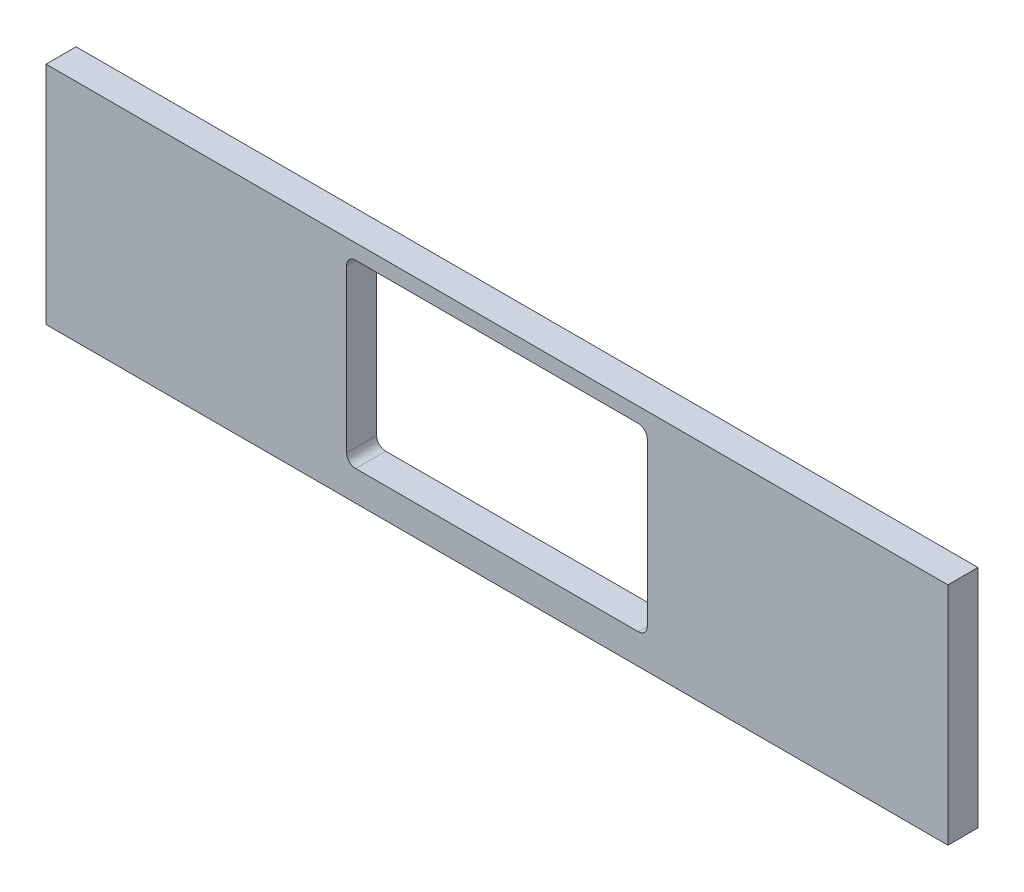
SolidWorks part; units mm, degrees
ref_plane "Ebene vorne" through (0, 0, 0) normal (0, 0, 1) x (1, 0, 0)
ref_plane "Ebene oben" through (0, 0, 0) normal (0, 1, 0) x (1, 0, 0)
ref_plane "Ebene rechts" through (0, 0, 0) normal (1, 0, 0) x (0, 0, -1)
sketch "Skizze1" plane through (0, 0, 0) normal (0, 0, 1) x (1, 0, 0)
  line L0 (-150, -75) -> (-150, 55) construction
  line L1 (150, -150) -> (-150, -150)
  line L2 (150, -150) -> (150, -75)
  line L3 (150, -75) -> (-150, -75)
  line L4 (-150, -150) -> (-150, -75)
  dimension "D1" = 75
extrude "Linear austragen1" add sketch "Skizze1" along normal blind 10
sketch "Skizze2" plane through (0, 0, 10) normal (0, 0, 1) x (1, 0, 0)
  line L0 (-150, -150) -> (150, -150) construction
  line L1 (50, -140) -> (-50, -140)
  line L2 (50, -140) -> (50, -80)
  line L3 (50, -80) -> (-50, -80)
  line L4 (-50, -140) -> (-50, -80)
  line L5 (50, -140) -> (150, -140) construction
  line L6 (150, 55) -> (150, -150) construction
  line L7 (-50, -140) -> (-150, -140) construction
  line L8 (-150, 55) -> (-150, -150) construction
  dimension "D1" = 10
  dimension "D2" = 100
  dimension "D3" = 60
extrude "Schnitt-Linear austragen1" cut sketch "Skizze2" against normal blind 10
fillet "Verrundung1" radius 3 4 edges at (-50, -140, 5) (50, -140, 5) (-50, -80, 5) (50, -80, 5)
